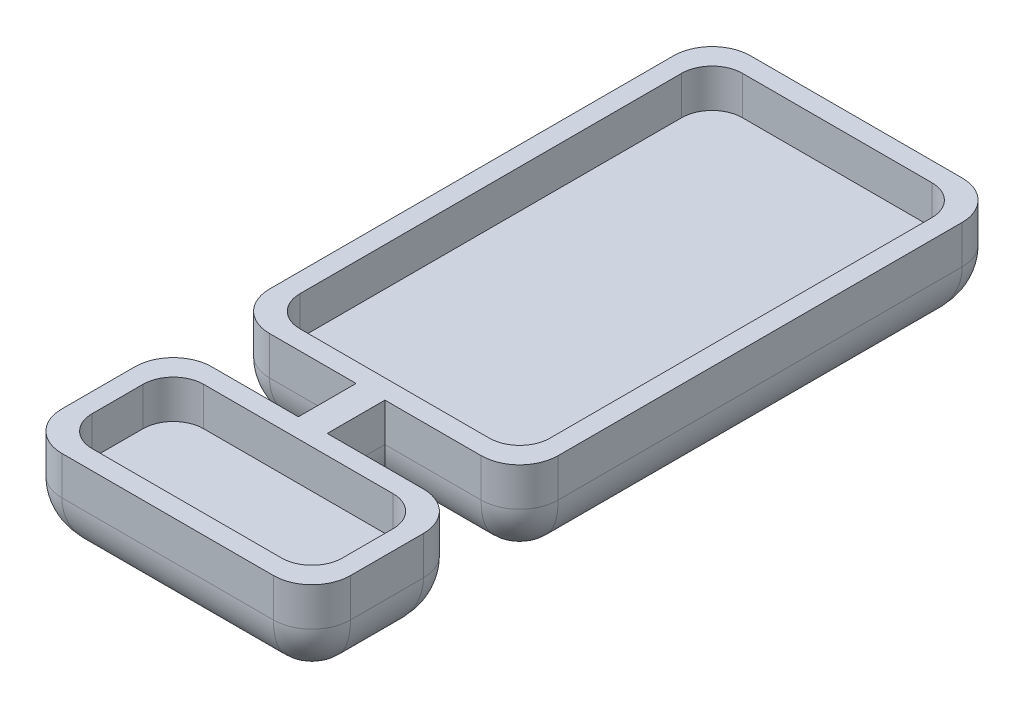
SolidWorks part; units mm, degrees
ref_plane "Front Plane" through (0, 0, 0) normal (0, 0, 1) x (1, 0, 0)
ref_plane "Top Plane" through (0, 0, 0) normal (0, 1, 0) x (1, 0, 0)
ref_plane "Right Plane" through (0, 0, 0) normal (1, 0, 0) x (0, 0, -1)
sketch "Sketch1" plane through (0, 0, 0) normal (0, 1, 0) x (1, 0, 0)
  line L0 (2, 0) -> (6.5, 0)
  line L2 (0, 2) -> (0, 23)
  line L3 (2, 25) -> (7.5, 25)
  line L4 (15, 2) -> (15, 23)
  line L9 (6.5, 0) -> (6.5, -3)
  line L10 (2, -3) -> (6.5, -3)
  line L11 (0, -5) -> (0, -8.7937)
  line L12 (2, -10.7937) -> (7.5, -10.7937)
  line L13 (15, -5) -> (15, -8.7937)
  line L14 (8, 0) -> (8, -3)
  line L15 (8, 0) -> (13, 0)
  line L16 (8, -3) -> (13, -3)
  line L23 (9.5, 25) -> (13, 25)
  line L30 (9.5, -10.7937) -> (13, -10.7937)
  line L31 (7.5, 25) -> (9.5, 25)
  line L32 (7.5, -10.7937) -> (9.5, -10.7937)
  arc A0 (13, -10.7937) -> (15, -8.7937) centre (13, -8.7937) ccw
  arc A1 (2, -10.7937) -> (0, -8.7937) centre (2, -8.7937) cw
  arc A2 (15, -5) -> (13, -3) centre (13, -5) ccw
  arc A3 (2, -3) -> (0, -5) centre (2, -5) ccw
  arc A4 (15, 2) -> (13, 0) centre (13, 2) cw
  arc A5 (2, 0) -> (0, 2) centre (2, 2) cw
  arc A6 (15, 23) -> (13, 25) centre (13, 23) ccw
  arc A7 (2, 25) -> (0, 23) centre (2, 23) ccw
  point P13 (8, -1.5)
  point P16 (15, -10.7937)
  point P19 (0, -10.7937)
  point P24 (0, -3)
  point P27 (15, 0)
  point P30 (0, 0)
  point P33 (15, 25)
  point P36 (0, 25)
  dimension "D7" = 2
  dimension "D8" = 2
  dimension "D9" = 2
  dimension "D10" = 2
  dimension "D11" = 2
  dimension "D12" = 2
  dimension "D13" = 2
  dimension "D14" = 2
  dimension "D1" = 15
  dimension "D2" = 25
  dimension "D3" = 15
  dimension "D4" = 7.7937
  dimension "D5" = 3
  dimension "D6" = 1.5
  dimension "D15" = 6.5
extrude "Boss-Extrude1" add sketch "Sketch1" along normal blind 5
fillet "Fillet1" radius 3 20 edges at (4.25, 0, 3) (0.5858, 0, 3.5858) (0, 0, 6.8969) (0.5858, 0, 10.2079) (7.5, 0, 10.7937) (14.4142, 0, 10.2079) (15, 0, 6.8969) (14.4142, 0, 3.5858) (10.5, 0, 3) (8, 0, 1.5) (10.5, 0, 0) (14.4142, 0, -0.5858) (15, 0, -12.5) (14.4142, 0, -24.4142) (7.5, 0, -25) (0.5858, 0, -24.4142) (0, 0, -12.5) (0.5858, 0, -0.5858) (4.25, 0, 0) (6.5, 0, 1.5)
sketch "Sketch2" plane through (0, 5, 0) normal (0, 1, 0) x (1, 0, 0)
  line L0 (13, 25) -> (2, 25) construction
  line L1 (2.5774, 24) -> (12.4226, 24)
  line L2 (1, 22.4226) -> (1, 2.5774)
  line L3 (2.5774, 1) -> (12.4226, 1)
  line L4 (14, 22.4226) -> (14, 2.5774)
  line L5 (2.5774, -4) -> (12.4226, -4)
  line L6 (1, -5.5774) -> (1, -8.2163)
  line L7 (2.5774, -9.7937) -> (12.4226, -9.7937)
  line L8 (14, -5.5774) -> (14, -8.2163)
  line L9 (15, 2) -> (15, 23) construction
  line L10 (0, 23) -> (0, 2) construction
  line L11 (8, 0) -> (13, 0) construction
  line L12 (15, -8.7937) -> (15, -5) construction
  line L13 (0, -5) -> (0, -8.7937) construction
  line L14 (2, -10.7937) -> (13, -10.7937) construction
  line L15 (6.5, -3) -> (2, -3) construction
  arc A0 (12.4226, -9.7937) -> (14, -8.2163) centre (12.4226, -8.2163) ccw
  arc A1 (2.5774, -9.7937) -> (1, -8.2163) centre (2.5774, -8.2163) cw
  arc A2 (14, -5.5774) -> (12.4226, -4) centre (12.4226, -5.5774) ccw
  arc A3 (2.5774, -4) -> (1, -5.5774) centre (2.5774, -5.5774) ccw
  arc A4 (14, 22.4226) -> (12.4226, 24) centre (12.4226, 22.4226) ccw
  arc A5 (2.5774, 24) -> (1, 22.4226) centre (2.5774, 22.4226) ccw
  arc A6 (12.4226, 1) -> (14, 2.5774) centre (12.4226, 2.5774) ccw
  arc A7 (2.5774, 1) -> (1, 2.5774) centre (2.5774, 2.5774) cw
  point P34 (1, -6.8969)
  dimension "D5" = 1.5774
  dimension "D6" = 1.5774
  dimension "D7" = 1.5774
  dimension "D8" = 1.5774
  dimension "D9" = 1.5774
  dimension "D10" = 1.5774
  dimension "D11" = 1.5774
  dimension "D12" = 1.5774
  dimension "D1" = 1
  dimension "D2" = 1
  dimension "D3" = 1
  dimension "D4" = 1
  dimension "D13" = 1
  dimension "D14" = 1
  dimension "D15" = 1
  dimension "D16" = 1
extrude "Cut-Extrude1" cut sketch "Sketch2" against normal blind 2
